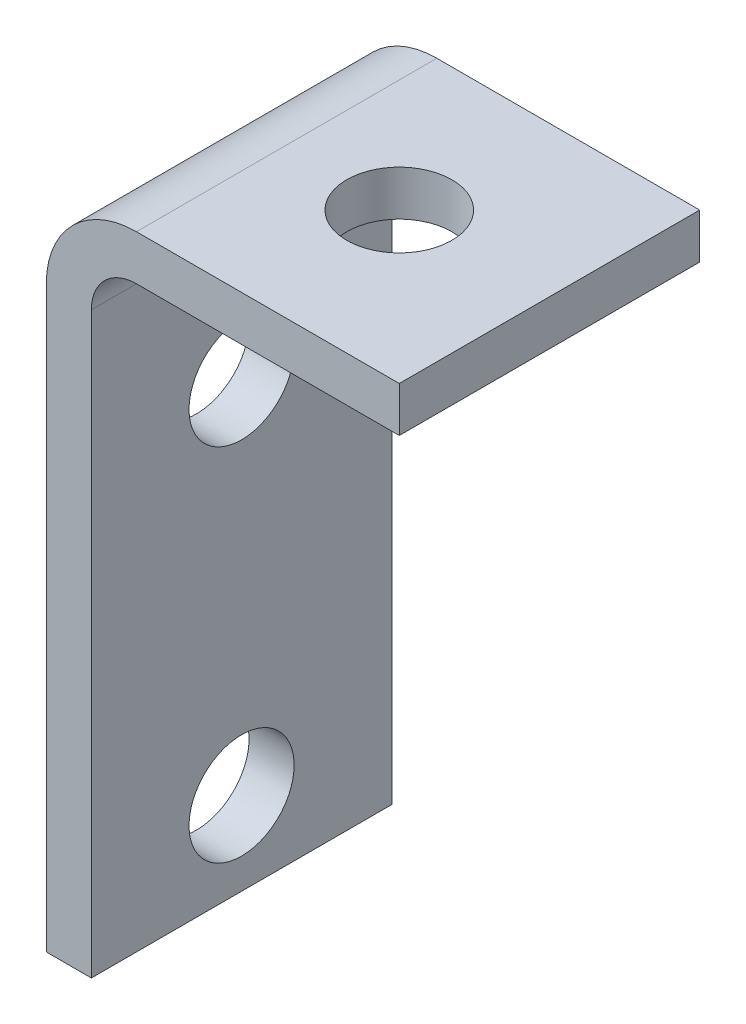
SolidWorks part; units mm, degrees
ref_plane "Front Plane" through (0, 0, 0) normal (0, 0, 1) x (1, 0, 0)
ref_plane "Top Plane" through (0, 0, 0) normal (0, 1, 0) x (1, 0, 0)
ref_plane "Right Plane" through (0, 0, 0) normal (1, 0, 0) x (0, 0, -1)
sketch "Sketch7" plane through (0, 0, 0) normal (0, 0, 1) x (1, 0, 0)
  line L0 (0, 0) -> (47, 0)
  line L1 (47, 0) -> (47, 89.0555)
  line L2 (47, 89.0555) -> (12, 89.0555)
  line L3 (0, 77.0555) -> (0, 0)
  arc A0 (12, 89.0555) -> (0, 77.0555) centre (12, 77.0555) ccw
  dimension "D1" = 12
  dimension "D2" = 47
  dimension "D3" = 89.0555
base flange "Base-Flange1" sketch "Sketch7" thickness 40 reverse thickness direction yes parameters "D1"=0
sketch "Sketch10" plane through (0, 0, -40) normal (0, 0, -1) x (-1, 0, 0)
  line L0 (-12, 83.0555) -> (-47, 83.0555)
  line L1 (-47, 83.0555) -> (-47, 0)
  line L2 (-47, 0) -> (-6, 0)
  line L3 (-6, 0) -> (-6, 77.0555)
  line L4 (-47, 89.0555) -> (-12, 89.0555) construction
  line L5 (0, 77.0555) -> (0, 0) construction
  arc A0 (-6, 77.0555) -> (-12, 83.0555) centre (-12, 77.0555) ccw
  dimension "D1" = 6
  dimension "D2" = 6
  dimension "D3" = 6
extrude "Cut-Extrude1" cut sketch "Sketch10" against normal through all
hole_wizard "Ø14.0 (14) Diameter Hole1" positions "Sketch12" profile "Sketch11" hole size "Ø14.0" standard "ANSI Metric"
sketch "Sketch12" plane through (0, 0, 0) normal (-1, 0, 0) x (0, 0, 1)
  line L2 (-20, 59.0555) -> (-20, 11.0555) construction
  line L4 (0, 77.0555) -> (0, 0) construction
  line L5 (-40, 77.0555) -> (-40, 0) construction
  line L6 (-40, 77.0555) -> (0, 77.0555) construction
  point P0 (-20, 59.0555)
  point P1 (-20, 11.0555)
  dimension "D1" = 48
  dimension "D2" = 18
sketch "Sketch11" plane through (0, 59.0555, -20) normal (0, 1, 0) x (0, 0, 1)
  line L0 (0, 0) -> (0, 47)
  line L1 (0, 47) -> (7, 47)
  line L2 (7, 47) -> (7, 0)
  line L5 (7, 0) -> (0, 0)
  line L11 (0, -6.35) -> (0, 107.95) construction
  dimension "Thru Hole Dia." = 14
  dimension "Thru Hole Depth" = 47
hole_wizard "Ø14.0 (14) Diameter Hole2" positions "Sketch14" profile "Sketch13" hole size "Ø14.0" standard "ANSI Metric"
sketch "Sketch14" plane through (0, 83.0555, 0) normal (0, -1, 0) x (-1, 0, 0)
  line L3 (-12, 20) -> (-47, 20) construction
  line L5 (-12, 0) -> (-12, 40) construction
  line L6 (-47, 0) -> (-47, 40) construction
  line L8 (-12, 0) -> (-47, 0) construction
  line L9 (-12, 40) -> (-47, 40) construction
  point P0 (-27, 20)
  dimension "D1" = 15
sketch "Sketch13" plane through (27, 83.0555, -20) normal (1, 0, 0) x (0, 0, -1)
  line L0 (0, 0) -> (0, 6)
  line L1 (0, 6) -> (7, 6)
  line L2 (7, 6) -> (7, 0)
  line L5 (7, 0) -> (0, 0)
  line L11 (0, -6.35) -> (0, 107.95) construction
  dimension "Thru Hole Dia." = 14
  dimension "Thru Hole Depth" = 6
sketch "Bend-Lines1" plane through (0, 0, 0) normal (0, 1, 0) x (1, 0, 0)
sketch "Bounding-Box1" plane through (0, 0, 0) normal (0, 1, 0) x (1, 0, 0)
sheet metal parameters "Sheet-Metal4" thickness 40 parameters "D1"=0
flat pattern "Flat-Pattern4" [suppressed]
sketch "Bend-Lines3" plane through (0, 0, 0) normal (0, 1, 0) x (1, 0, 0)
sketch "Bounding-Box3" [suppressed] plane through (0, 0, 0) normal (0, 1, 0) x (1, 0, 0)
sheet metal parameters "Sheet-Metal5" thickness 40 parameters "D1"=0
flat pattern "Flat-Pattern4"
sketch "Bend-Lines3" plane through (0, 0, 0) normal (0, 1, 0) x (1, 0, 0)
sketch "Bounding-Box3" [suppressed] plane through (0, 0, 0) normal (0, 1, 0) x (1, 0, 0)
sheet metal parameters "Sheet-Metal6" thickness 40 parameters "D1"=0
flat pattern "Flat-Pattern4"
sketch "Bend-Lines3" plane through (0, 0, 0) normal (0, 1, 0) x (1, 0, 0)
sketch "Bounding-Box3" [suppressed] plane through (0, 0, 0) normal (0, 1, 0) x (1, 0, 0)
sheet metal parameters "Sheet-Metal7" thickness 40 parameters "D1"=0
flat pattern "Flat-Pattern4"
sketch "Bend-Lines3" plane through (0, 0, 0) normal (0, 1, 0) x (1, 0, 0)
sketch "Bounding-Box3" [suppressed] plane through (0, 0, 0) normal (0, 1, 0) x (1, 0, 0)
